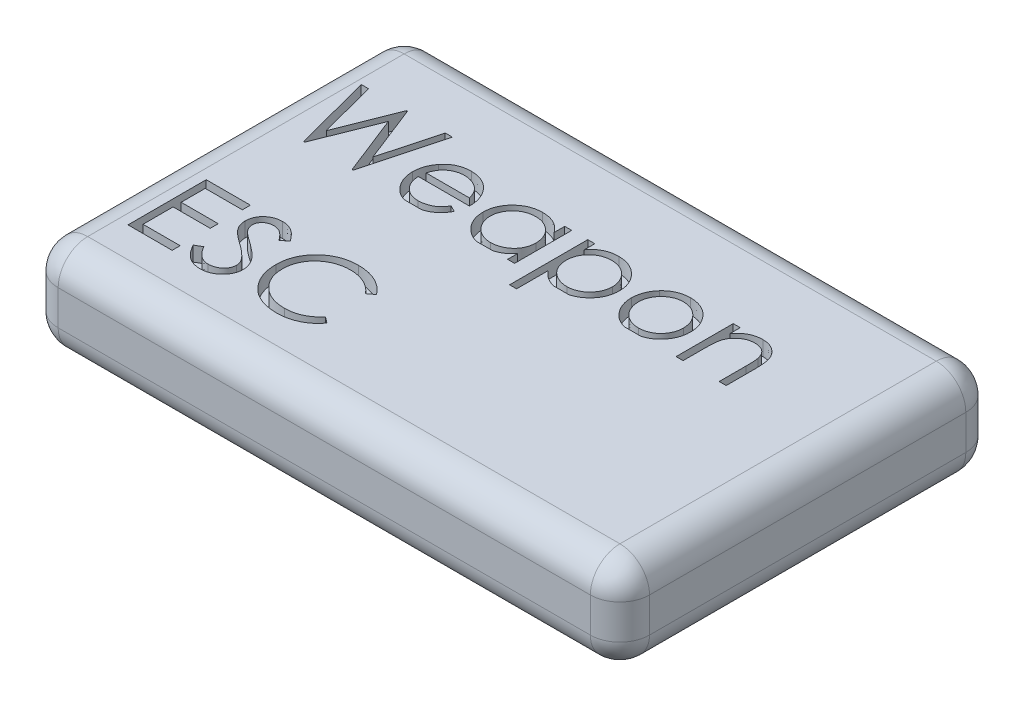
SolidWorks part; units mm, degrees
ref_plane "Front Plane" through (0, 0, 0) normal (0, 0, 1) x (1, 0, 0)
ref_plane "Top Plane" through (0, 0, 0) normal (0, 1, 0) x (1, 0, 0)
ref_plane "Right Plane" through (0, 0, 0) normal (1, 0, 0) x (0, 0, -1)
sketch "Sketch1" plane through (0, 0, 0) normal (0, 1, 0) x (1, 0, 0)
  line L1 (0, 0) -> (20, 0)
  line L2 (0, 0) -> (0, 12.7)
  line L3 (0, 12.7) -> (20, 12.7)
  line L4 (20, 0) -> (20, 12.7)
  dimension "D1" = 20
  dimension "D2" = 12.7
extrude "Boss-Extrude1" add sketch "Sketch1" along normal blind 3.175
fillet "Fillet1" radius 1 12 edges at (0, 0, -6.35) (10, 0, 0) (20, 0, -6.35) (10, 0, -12.7) (20, 3.175, -6.35) (10, 3.175, -12.7) (0, 1.5875, -12.7) (20, 1.5875, -12.7) (20, 1.5875, 0) (0, 1.5875, 0) (0, 3.175, -6.35) (10, 3.175, 0)
sketch "Sketch2" plane through (0, 3.175, 0) normal (0, 1, 0) x (1, 0, 0)
  line L0 (1, 7.4323) -> (19, 7.4323)
  line L1 (1, 11.7) -> (1, 1) construction
  line L2 (19, 1) -> (19, 11.7) construction
  line L3 (1.1696, 10.0782) -> (1.415, 10.0782)
  line L4 (1.415, 10.0782) -> (1.9328, 8.1378)
  line L5 (1.9328, 8.1378) -> (2.7029, 10.0782)
  line L6 (2.7029, 10.0782) -> (2.7374, 10.0782)
  line L7 (2.7374, 10.0782) -> (3.4932, 8.151)
  line L8 (3.4932, 8.151) -> (4.0137, 10.0782)
  line L9 (4.0137, 10.0782) -> (4.2564, 10.0782)
  line L10 (4.2564, 10.0782) -> (3.543, 7.4323)
  line L11 (3.543, 7.4323) -> (3.5091, 7.4323)
  line L12 (3.5091, 7.4323) -> (2.713, 9.4559)
  line L13 (2.713, 9.4559) -> (1.9074, 7.4323)
  line L14 (1.9074, 7.4323) -> (1.8735, 7.4323)
  line L15 (1.8735, 7.4323) -> (1.1696, 10.0782)
  line L16 (6.2503, 8.0429) -> (6.4613, 7.9321)
  line L17 (6.563, 8.3482) -> (4.8331, 8.3482)
  line L18 (4.858, 8.5856) -> (6.3256, 8.5856)
  line L19 (9.0053, 9.3658) -> (9.0053, 7.4323)
  line L20 (9.0053, 7.4323) -> (8.7679, 7.4323)
  line L21 (8.7679, 7.4323) -> (8.7679, 7.7668)
  line L22 (8.7679, 9.0081) -> (8.7679, 9.3658)
  line L23 (8.7679, 9.3658) -> (9.0053, 9.3658)
  line L24 (9.5481, 9.3658) -> (9.7855, 9.3658)
  line L25 (9.7855, 9.3658) -> (9.7855, 9.0081)
  line L26 (9.7855, 7.7827) -> (9.7855, 6.72)
  line L27 (9.7855, 6.72) -> (9.5481, 6.72)
  line L28 (9.5481, 6.72) -> (9.5481, 9.3658)
  line L29 (14.4666, 9.3658) -> (14.7041, 9.3658)
  line L30 (14.7041, 9.3658) -> (14.7041, 9.0171)
  line L31 (16.1627, 8.4197) -> (16.1627, 7.4323)
  line L32 (16.1627, 7.4323) -> (15.9252, 7.4323)
  line L33 (15.9252, 7.4323) -> (15.9252, 8.3418)
  line L34 (14.7041, 8.1314) -> (14.7041, 7.4323)
  line L35 (14.7041, 7.4323) -> (14.4666, 7.4323)
  line L36 (14.4666, 7.4323) -> (14.4666, 9.3658)
  line L37 (1.3392, 4.6684) -> (2.8317, 4.6684)
  line L38 (2.8317, 4.6684) -> (2.8317, 4.3971)
  line L39 (2.8317, 4.3971) -> (1.5767, 4.3971)
  line L40 (1.5767, 4.3971) -> (1.5767, 3.583)
  line L41 (1.5767, 3.583) -> (2.8317, 3.583)
  line L42 (2.8317, 3.583) -> (2.8317, 3.3116)
  line L43 (2.8317, 3.3116) -> (1.5767, 3.3116)
  line L44 (1.5767, 3.3116) -> (1.5767, 2.294)
  line L45 (1.5767, 2.294) -> (2.8317, 2.294)
  line L46 (2.8317, 2.294) -> (2.8317, 2.0226)
  line L47 (2.8317, 2.0226) -> (1.3392, 2.0226)
  line L48 (1.3392, 2.0226) -> (1.3392, 4.6684)
  line L49 (3.0353, 2.533) -> (3.2589, 2.6671)
  line L50 (4.5617, 4.2884) -> (4.347, 4.1257)
  line L51 (7.5807, 4.1829) -> (7.3729, 4.0239)
  line L52 (7.3729, 2.6671) -> (7.5807, 2.5097)
  spline S0 degree 3 poles (6.4613, 7.9321) (6.4299, 7.8734) (6.3774, 7.791) (6.2965, 7.6929) (6.2322, 7.6311) (6.1644, 7.5772) (6.0928, 7.5301) (6.017, 7.49) (5.937, 7.4561) (5.8521, 7.4301) (5.7293, 7.405) (5.6334, 7.3984) (5.5682, 7.3984) knots 0 0 0 0 0.181661 0.265874 0.346355 0.4246 0.501903 0.579992 0.658443 0.738672 0.821894 1 1 1 1
  spline S1 degree 3 poles (5.5682, 7.3984) (5.4958, 7.3984) (5.3893, 7.4067) (5.2538, 7.4394) (5.1606, 7.4726) (5.0739, 7.516) (4.9934, 7.5689) (4.9187, 7.631) (4.8521, 7.7028) (4.7922, 7.7797) (4.7394, 7.8597) (4.6952, 7.9429) (4.6592, 8.0285) (4.6302, 8.1161) (4.6029, 8.2374) (4.5963, 8.331) (4.5956, 8.3938) knots 0 0 0 0 0.139629 0.204797 0.268135 0.329814 0.391301 0.453434 0.516552 0.579631 0.641119 0.701294 0.76081 0.819932 0.87892 1 1 1 1
  spline S2 degree 3 poles (4.5956, 8.3938) (4.5963, 8.4526) (4.6018, 8.5404) (4.6257, 8.6542) (4.6501, 8.7365) (4.6815, 8.8163) (4.733, 8.9202) (4.7823, 8.9928) (4.8182, 9.0393) knots 0 0 0 0 0.253768 0.377428 0.500551 0.623296 0.746578 1 1 1 1
  spline S3 degree 3 poles (4.8182, 9.0393) (4.864, 9.0966) (4.9387, 9.1766) (5.0556, 9.2603) (5.1475, 9.3118) (5.246, 9.3508) (5.3871, 9.3905) (5.4988, 9.3988) (5.574, 9.3997) knots 0 0 0 0 0.253589 0.374643 0.49534 0.616325 0.739759 1 1 1 1
  spline S4 degree 3 poles (5.574, 9.3997) (5.6518, 9.4001) (5.7666, 9.3888) (5.9122, 9.3485) (6.0134, 9.3069) (6.1084, 9.2531) (6.228, 9.163) (6.3062, 9.0802) (6.3526, 9.0192) knots 0 0 0 0 0.259033 0.38188 0.502258 0.622752 0.744743 1 1 1 1
  spline S5 degree 3 poles (6.3526, 9.0192) (6.3873, 8.9747) (6.4326, 8.9024) (6.4807, 8.799) (6.5097, 8.7167) (6.5331, 8.6306) (6.5563, 8.5079) (6.5618, 8.4126) (6.563, 8.3482) knots 0 0 0 0 0.236255 0.356174 0.47725 0.60154 0.729618 1 1 1 1
  spline S6 degree 3 poles (4.8331, 8.3482) (4.8344, 8.2981) (4.8411, 8.2241) (4.864, 8.1295) (4.8876, 8.0636) (4.9163, 8.001) (4.9513, 7.9419) (4.9932, 7.8867) (5.0398, 7.8348) (5.0918, 7.7887) (5.1464, 7.7473) (5.2045, 7.7127) (5.2657, 7.6846) (5.3298, 7.6626) (5.4205, 7.6422) (5.4909, 7.6356) (5.5385, 7.6358) knots 0 0 0 0 0.134476 0.198391 0.260753 0.321829 0.383037 0.444653 0.507398 0.569825 0.630778 0.690929 0.750945 0.811049 0.872331 1 1 1 1
  spline S7 degree 3 poles (5.5385, 7.6358) (5.5855, 7.6356) (5.6561, 7.6412) (5.7482, 7.6604) (5.8156, 7.68) (5.8803, 7.7039) (5.9402, 7.7327) (5.9953, 7.7645) (6.0468, 7.801) (6.0968, 7.8456) (6.1674, 7.9248) (6.2182, 7.9926) (6.2503, 8.0429) knots 0 0 0 0 0.163879 0.245659 0.327726 0.40861 0.485749 0.559169 0.630268 0.705306 0.792065 1 1 1 1
  spline S8 degree 3 poles (6.3256, 8.5856) (6.3106, 8.6467) (6.2806, 8.7328) (6.2258, 8.8363) (6.1793, 8.901) (6.1265, 8.9584) (6.0655, 9.0087) (5.9972, 9.0536) (5.9217, 9.0915) (5.8419, 9.1237) (5.7302, 9.1529) (5.644, 9.1632) (5.5862, 9.1623) knots 0 0 0 0 0.185231 0.267501 0.3444 0.419595 0.496891 0.576638 0.660268 0.745387 0.83004 1 1 1 1
  spline S9 degree 3 poles (5.5862, 9.1623) (5.5394, 9.1624) (5.4698, 9.1573) (5.3804, 9.1379) (5.3163, 9.1183) (5.2554, 9.0921) (5.176, 9.051) (5.1224, 9.01) (5.088, 8.981) knots 0 0 0 0 0.259141 0.384162 0.505992 0.629098 0.750669 1 1 1 1
  spline S10 degree 3 poles (5.088, 8.981) (5.0616, 8.9588) (5.0259, 8.9203) (4.9831, 8.8638) (4.9533, 8.8162) (4.926, 8.7643) (4.8911, 8.6882) (4.8704, 8.6275) (4.858, 8.5856) knots 0 0 0 0 0.22258 0.3385 0.458709 0.585535 0.717518 1 1 1 1
  spline S11 degree 3 poles (8.7679, 7.7668) (8.7171, 7.7067) (8.635, 7.6231) (8.5091, 7.5365) (8.4118, 7.4849) (8.3098, 7.4463) (8.1661, 7.4089) (8.0539, 7.3978) (7.9782, 7.3984) knots 0 0 0 0 0.262085 0.38627 0.507165 0.6273 0.748145 1 1 1 1
  spline S12 degree 3 poles (7.9782, 7.3984) (7.9109, 7.3986) (7.8109, 7.4073) (7.6823, 7.4381) (7.5906, 7.4698) (7.5032, 7.5118) (7.4192, 7.5621) (7.3392, 7.622) (7.2643, 7.6905) (7.1954, 7.7649) (7.1348, 7.8442) (7.0844, 7.9282) (7.0422, 8.0156) (7.0097, 8.1073) (6.9789, 8.2364) (6.9702, 8.3367) (6.9701, 8.4044) knots 0 0 0 0 0.127433 0.189004 0.24993 0.310668 0.372329 0.434939 0.499576 0.564191 0.626735 0.688109 0.749294 0.810331 0.871901 1 1 1 1
  spline S13 degree 3 poles (6.9701, 8.4044) (6.9705, 8.4708) (6.9786, 8.5695) (7.0103, 8.6963) (7.0432, 8.7865) (7.0854, 8.873) (7.1368, 8.9557) (7.1973, 9.0349) (7.267, 9.1087) (7.3426, 9.1769) (7.4234, 9.2362) (7.5075, 9.2874) (7.5961, 9.3279) (7.688, 9.3607) (7.8174, 9.3915) (7.918, 9.3991) (7.9856, 9.3997) knots 0 0 0 0 0.126079 0.186904 0.247574 0.308003 0.369132 0.432033 0.496791 0.561611 0.624914 0.686726 0.748079 0.809582 0.871631 1 1 1 1
  spline S14 degree 3 poles (7.9856, 9.3997) (8.0628, 9.3995) (8.1776, 9.3896) (8.3227, 9.3488) (8.4245, 9.3081) (8.5206, 9.2539) (8.643, 9.1608) (8.7211, 9.0723) (8.7679, 9.0081) knots 0 0 0 0 0.254654 0.376015 0.495255 0.614798 0.738106 1 1 1 1
  spline S15 degree 3 poles (7.9888, 9.1623) (7.9204, 9.162) (7.818, 9.1506) (7.6887, 9.1079) (7.5973, 9.0646) (7.5121, 9.0102) (7.436, 8.9443) (7.3683, 8.8688) (7.3114, 8.7841) (7.265, 8.6932) (7.2213, 8.5669) (7.2067, 8.4678) (7.2075, 8.4017) knots 0 0 0 0 0.169593 0.252476 0.336244 0.419505 0.502036 0.584775 0.669846 0.754185 0.836658 1 1 1 1
  spline S16 degree 3 poles (7.2075, 8.4017) (7.2081, 8.336) (7.2207, 8.2366) (7.2659, 8.1105) (7.3122, 8.0188) (7.3702, 7.9337) (7.4374, 7.8568) (7.5144, 7.7907) (7.5998, 7.7353) (7.691, 7.6906) (7.8191, 7.6488) (7.9194, 7.6355) (7.9867, 7.6358) knots 0 0 0 0 0.162859 0.245484 0.330807 0.416493 0.499893 0.583048 0.667158 0.751312 0.833785 1 1 1 1
  spline S17 degree 3 poles (7.9867, 7.6358) (8.0549, 7.6361) (8.1575, 7.648) (8.2881, 7.6903) (8.3817, 7.734) (8.4689, 7.7883) (8.5471, 7.8518) (8.6132, 7.9257) (8.6693, 8.0068) (8.7133, 8.0958) (8.7568, 8.2239) (8.7675, 8.3263) (8.7679, 8.3948) knots 0 0 0 0 0.168664 0.252552 0.33824 0.423103 0.505556 0.586176 0.667136 0.748499 0.830452 1 1 1 1
  spline S18 degree 3 poles (8.7679, 8.3948) (8.7677, 8.4474) (8.7611, 8.5253) (8.7375, 8.6252) (8.713, 8.6958) (8.6809, 8.7629) (8.6422, 8.8267) (8.5961, 8.8871) (8.5435, 8.9431) (8.4859, 8.9942) (8.425, 9.0399) (8.36, 9.0774) (8.2921, 9.1084) (8.221, 9.133) (8.12, 9.1555) (8.0418, 9.1631) (7.9888, 9.1623) knots 0 0 0 0 0.129188 0.191219 0.251913 0.312507 0.373494 0.435152 0.498741 0.562095 0.624187 0.685476 0.746097 0.807612 0.869967 1 1 1 1
  spline S19 degree 3 poles (9.7855, 9.0081) (9.8325, 9.0725) (9.9115, 9.1602) (10.0334, 9.2541) (10.1295, 9.308) (10.2311, 9.3487) (10.3757, 9.3896) (10.4899, 9.3995) (10.5668, 9.3997) knots 0 0 0 0 0.263045 0.386061 0.505771 0.625178 0.746148 1 1 1 1
  spline S20 degree 3 poles (10.5668, 9.3997) (10.6345, 9.3991) (10.7353, 9.3915) (10.8649, 9.3607) (10.9568, 9.3279) (11.0454, 9.2874) (11.1295, 9.2362) (11.2103, 9.1769) (11.2859, 9.1087) (11.3556, 9.0349) (11.416, 8.9555) (11.4681, 8.8731) (11.5102, 8.7865) (11.5431, 8.6963) (11.5748, 8.5695) (11.5829, 8.4708) (11.5833, 8.4044) knots 0 0 0 0 0.128636 0.190653 0.252125 0.313446 0.375227 0.438498 0.503285 0.56801 0.630879 0.692154 0.752552 0.813191 0.873985 1 1 1 1
  spline S21 degree 3 poles (11.5833, 8.4044) (11.5832, 8.3367) (11.5745, 8.2364) (11.5437, 8.1073) (11.5112, 8.0157) (11.4691, 7.928) (11.418, 7.8444) (11.3576, 7.7648) (11.2886, 7.6905) (11.2137, 7.622) (11.1336, 7.5621) (11.0497, 7.5118) (10.9622, 7.4698) (10.8706, 7.4381) (10.7418, 7.4072) (10.6417, 7.3986) (10.5742, 7.3984) knots 0 0 0 0 0.128034 0.189574 0.25058 0.311733 0.37325 0.435763 0.500346 0.564949 0.627528 0.689157 0.749865 0.81076 0.8723 1 1 1 1
  spline S22 degree 3 poles (10.5742, 7.3984) (10.4982, 7.3975) (10.386, 7.4105) (10.2421, 7.4502) (10.1406, 7.493) (10.0438, 7.5477) (9.919, 7.638) (9.8366, 7.7221) (9.7855, 7.7827) knots 0 0 0 0 0.250548 0.37123 0.492116 0.613401 0.737997 1 1 1 1
  spline S23 degree 3 poles (10.5646, 9.1623) (10.5116, 9.1631) (10.4335, 9.1555) (10.3324, 9.1331) (10.2613, 9.1082) (10.193, 9.0777) (10.1283, 9.0395) (10.067, 8.9944) (10.0094, 8.9433) (9.9573, 8.8869) (9.9112, 8.8267) (9.8725, 8.7628) (9.8404, 8.6958) (9.816, 8.6252) (9.7924, 8.5253) (9.7857, 8.4474) (9.7855, 8.3948) knots 0 0 0 0 0.130024 0.192374 0.253884 0.314896 0.375806 0.438242 0.501591 0.564881 0.626533 0.687516 0.748106 0.808796 0.870822 1 1 1 1
  spline S24 degree 3 poles (9.7855, 8.3948) (9.7856, 8.3262) (9.7971, 8.2241) (9.8394, 8.0957) (9.8836, 8.0069) (9.9396, 7.9253) (10.0069, 7.8522) (10.0851, 7.7881) (10.1728, 7.7341) (10.2669, 7.6903) (10.3978, 7.6482) (10.5002, 7.636) (10.5684, 7.6358) knots 0 0 0 0 0.169344 0.251061 0.332326 0.413189 0.494299 0.576654 0.661785 0.747765 0.831967 1 1 1 1
  spline S25 degree 3 poles (10.5684, 7.6358) (10.6352, 7.6354) (10.7352, 7.649) (10.8629, 7.6905) (10.9537, 7.7355) (11.039, 7.7907) (11.116, 7.8568) (11.1833, 7.9336) (11.2407, 8.019) (11.2868, 8.1106) (11.3331, 8.2364) (11.3451, 8.3361) (11.3459, 8.4017) knots 0 0 0 0 0.165574 0.248159 0.332033 0.416257 0.499525 0.583039 0.668596 0.754035 0.83692 1 1 1 1
  spline S26 degree 3 poles (11.3459, 8.4017) (11.3468, 8.4679) (11.332, 8.5668) (11.2885, 8.6934) (11.2413, 8.7838) (11.1852, 8.869) (11.1174, 8.9443) (11.0413, 9.0102) (10.9561, 9.0646) (10.8647, 9.1079) (10.7354, 9.1506) (10.6331, 9.162) (10.5646, 9.1623) knots 0 0 0 0 0.163349 0.245826 0.330367 0.415198 0.497941 0.580476 0.66374 0.747513 0.830399 1 1 1 1
  spline S27 degree 3 poles (12.9921, 9.3997) (13.0632, 9.4005) (13.1685, 9.3902) (13.3031, 9.3565) (13.3982, 9.3223) (13.4877, 9.2764) (13.6029, 9.2026) (13.6797, 9.1326) (13.7267, 9.0812) knots 0 0 0 0 0.258332 0.382134 0.503804 0.624693 0.746871 1 1 1 1
  spline S28 degree 3 poles (13.7267, 9.0812) (13.7698, 9.0341) (13.8276, 8.9585) (13.8897, 8.8494) (13.9269, 8.7646) (13.9561, 8.6766) (13.9842, 8.5534) (13.9914, 8.458) (13.9917, 8.3938) knots 0 0 0 0 0.253834 0.376506 0.498534 0.621368 0.744565 1 1 1 1
  spline S29 degree 3 poles (13.9917, 8.3938) (13.9921, 8.3291) (13.9833, 8.233) (13.954, 8.1087) (13.9232, 8.0196) (13.8836, 7.9335) (13.8353, 7.8508) (13.778, 7.7713) (13.713, 7.6957) (13.6411, 7.6261) (13.5632, 7.5653) (13.4806, 7.5133) (13.3925, 7.4714) (13.2994, 7.4384) (13.1663, 7.4067) (13.0624, 7.3987) (12.9921, 7.3984) knots 0 0 0 0 0.123337 0.183265 0.243172 0.302898 0.363774 0.425605 0.489659 0.553785 0.616222 0.677854 0.739517 0.802097 0.865866 1 1 1 1
  spline S30 degree 3 poles (12.9921, 7.3984) (12.9215, 7.3987) (12.8172, 7.4067) (12.6837, 7.4384) (12.5906, 7.4715) (12.502, 7.5133) (12.419, 7.5652) (12.341, 7.6261) (12.2691, 7.6957) (12.2041, 7.7713) (12.1468, 7.8508) (12.0985, 7.9335) (12.0589, 8.0196) (12.0281, 8.1087) (11.9989, 8.233) (11.99, 8.3291) (11.9904, 8.3938) knots 0 0 0 0 0.134635 0.198324 0.260825 0.322714 0.384555 0.446913 0.510958 0.574931 0.636685 0.697483 0.757134 0.816966 0.876818 1 1 1 1
  spline S31 degree 3 poles (11.9904, 8.3938) (11.9908, 8.4578) (11.998, 8.553) (12.026, 8.6759) (12.0552, 8.7635) (12.0927, 8.848) (12.154, 8.9574) (12.2127, 9.0324) (12.2554, 9.0796) knots 0 0 0 0 0.255238 0.378679 0.501088 0.622714 0.746241 1 1 1 1
  spline S32 degree 3 poles (12.2554, 9.0796) (12.302, 9.1317) (12.3795, 9.2011) (12.4944, 9.2763) (12.5849, 9.3213) (12.6799, 9.3567) (12.8151, 9.3902) (12.9206, 9.4004) (12.9921, 9.3997) knots 0 0 0 0 0.252713 0.374819 0.496436 0.617911 0.741288 1 1 1 1
  spline S33 degree 3 poles (12.9911, 9.1623) (12.9404, 9.1622) (12.8652, 9.1553) (12.7684, 9.1318) (12.6993, 9.1072) (12.6331, 9.0754) (12.5696, 9.0363) (12.5088, 8.9904) (12.4518, 8.9379) (12.3995, 8.8806) (12.3538, 8.8194) (12.3149, 8.7556) (12.2826, 8.6888) (12.2585, 8.6186) (12.2347, 8.5202) (12.228, 8.4437) (12.2278, 8.3922) knots 0 0 0 0 0.126044 0.187165 0.247399 0.30838 0.36978 0.432584 0.497641 0.562401 0.625557 0.687332 0.748313 0.809791 0.871768 1 1 1 1
  spline S34 degree 3 poles (12.2278, 8.3922) (12.228, 8.3251) (12.2398, 8.2244) (12.2839, 8.0974) (12.3281, 8.007) (12.3836, 7.9233) (12.449, 7.8487) (12.5236, 7.7843) (12.6065, 7.7309) (12.6959, 7.6885) (12.8232, 7.6477) (12.9235, 7.6351) (12.9911, 7.6358) knots 0 0 0 0 0.168179 0.251488 0.335841 0.419834 0.502345 0.583649 0.665931 0.748717 0.831047 1 1 1 1
  spline S35 degree 3 poles (12.9911, 7.6358) (13.0585, 7.6352) (13.1588, 7.6475) (13.2858, 7.6886) (13.3752, 7.7308) (13.458, 7.7845) (13.5331, 7.8483) (13.5979, 7.9235) (13.6534, 8.0071) (13.6983, 8.0972) (13.7422, 8.2244) (13.7542, 8.3251) (13.7543, 8.3922) knots 0 0 0 0 0.168983 0.250908 0.333708 0.416005 0.49766 0.579893 0.663902 0.748466 0.831791 1 1 1 1
  spline S36 degree 3 poles (13.7543, 8.3922) (13.7541, 8.4437) (13.7474, 8.5202) (13.7237, 8.6186) (13.6995, 8.6888) (13.6673, 8.7557) (13.6276, 8.8193) (13.5821, 8.8808) (13.5292, 8.9377) (13.4723, 8.9904) (13.4114, 9.0363) (13.3481, 9.0752) (13.282, 9.1075) (13.2129, 9.1316) (13.1165, 9.1555) (13.0415, 9.162) (12.9911, 9.1623) knots 0 0 0 0 0.128274 0.19027 0.251768 0.312769 0.374793 0.43797 0.503047 0.568125 0.63095 0.692369 0.752973 0.813641 0.874355 1 1 1 1
  spline S37 degree 3 poles (14.7041, 9.0171) (14.752, 9.0792) (14.8282, 9.1661) (14.9472, 9.2572) (15.0378, 9.3102) (15.1328, 9.3501) (15.2655, 9.3891) (15.3698, 9.3994) (15.4397, 9.3997) knots 0 0 0 0 0.273569 0.398988 0.51993 0.63811 0.756589 1 1 1 1
  spline S38 degree 3 poles (15.4397, 9.3997) (15.5096, 9.3993) (15.6138, 9.3879) (15.7427, 9.3405) (15.8309, 9.2928) (15.9104, 9.2333) (15.9801, 9.1641) (16.0379, 9.0845) (16.0766, 9.0106) (16.1021, 8.9451) (16.1181, 8.8889) (16.1317, 8.8264) (16.1436, 8.7577) (16.1516, 8.6822) (16.1603, 8.569) (16.1632, 8.4807) (16.1627, 8.4197) knots 0 0 0 0 0.151178 0.223488 0.295543 0.366976 0.437131 0.507044 0.57856 0.616614 0.658756 0.704491 0.754803 0.809332 0.868274 1 1 1 1
  spline S39 degree 3 poles (15.9252, 8.3418) (15.9248, 8.3922) (15.9248, 8.4643) (15.9218, 8.556) (15.9188, 8.6145) (15.9144, 8.6661) (15.9089, 8.7212) (15.9025, 8.759) (15.8971, 8.7817) knots 0 0 0 0 0.34211 0.489826 0.623254 0.74008 0.841483 1 1 1 1
  spline S40 degree 3 poles (15.8971, 8.7817) (15.8839, 8.8398) (15.8539, 8.9227) (15.7872, 9.0146) (15.7283, 9.0692) (15.6593, 9.1116) (15.5502, 9.1526) (15.4601, 9.1626) (15.3984, 9.1623) knots 0 0 0 0 0.260833 0.378476 0.493178 0.609281 0.729981 1 1 1 1
  spline S41 degree 3 poles (15.3984, 9.1623) (15.3606, 9.1625) (15.3041, 9.1582) (15.2311, 9.1424) (15.1778, 9.1266) (15.1268, 9.1049) (15.0763, 9.0804) (15.0283, 9.0497) (14.9817, 9.0155) (14.9384, 8.9777) (14.8981, 8.9377) (14.8622, 8.8952) (14.8296, 8.8507) (14.8015, 8.8038) (14.7686, 8.7382) (14.7501, 8.686) (14.7406, 8.6503) knots 0 0 0 0 0.126627 0.188984 0.25023 0.312351 0.374574 0.438148 0.50292 0.567974 0.630771 0.692935 0.754398 0.815218 0.876117 1 1 1 1
  spline S42 degree 3 poles (14.7406, 8.6503) (14.7336, 8.622) (14.7257, 8.5756) (14.7178, 8.5083) (14.7125, 8.4472) (14.7092, 8.3786) (14.7043, 8.2726) (14.7044, 8.1893) (14.7041, 8.1314) knots 0 0 0 0 0.167615 0.271052 0.38946 0.520843 0.666399 1 1 1 1
  spline S43 degree 3 poles (3.2589, 2.6671) (3.2977, 2.5999) (3.3588, 2.5056) (3.455, 2.3988) (3.5268, 2.3361) (3.6011, 2.2869) (3.7031, 2.2404) (3.7854, 2.226) (3.8398, 2.2261) knots 0 0 0 0 0.304646 0.438547 0.562322 0.677433 0.786897 1 1 1 1
  spline S44 degree 3 poles (3.8398, 2.2261) (3.8858, 2.2257) (3.9544, 2.2338) (4.0425, 2.2593) (4.1049, 2.2863) (4.1632, 2.3191) (4.2143, 2.3587) (4.2585, 2.403) (4.2946, 2.4524) (4.3223, 2.5056) (4.3508, 2.5782) (4.3575, 2.6364) (4.3582, 2.6745) knots 0 0 0 0 0.18093 0.270088 0.360156 0.448343 0.532666 0.613834 0.693982 0.772716 0.849335 1 1 1 1
  spline S45 degree 3 poles (4.3582, 2.6745) (4.3584, 2.7193) (4.3404, 2.8129) (4.2921, 2.8948) (4.2633, 2.9342) knots 0 0 0 0 0.477158 1 1 1 1
  spline S46 degree 3 poles (4.2633, 2.9342) (4.2389, 2.9664) (4.1977, 3.0152) (4.1336, 3.0774) (4.0778, 3.1296) (4.0142, 3.1827) (3.9183, 3.261) (3.8402, 3.3173) (3.7863, 3.3561) knots 0 0 0 0 0.18953 0.299198 0.418926 0.548376 0.688136 1 1 1 1
  spline S47 degree 3 poles (3.7863, 3.3561) (3.7327, 3.3936) (3.6578, 3.4492) (3.5642, 3.5216) (3.5058, 3.5686) (3.4557, 3.6114) (3.4035, 3.6581) (3.371, 3.6934) (3.3527, 3.716) knots 0 0 0 0 0.347082 0.495568 0.628357 0.74552 0.845831 1 1 1 1
  spline S48 degree 3 poles (3.3527, 3.716) (3.3293, 3.7463) (3.2967, 3.7928) (3.2619, 3.8591) (3.2416, 3.9093) (3.2246, 3.9602) (3.2092, 4.0297) (3.2047, 4.0831) (3.2049, 4.1188) knots 0 0 0 0 0.262559 0.388264 0.512667 0.633722 0.755394 1 1 1 1
  spline S49 degree 3 poles (3.2049, 4.1188) (3.2047, 4.1742) (3.2152, 4.2565) (3.2504, 4.3603) (3.2869, 4.4332) (3.3339, 4.4997) (3.3884, 4.5606) (3.4533, 4.6118) (3.5245, 4.6566) (3.6024, 4.6916) (3.712, 4.7273) (3.799, 4.7355) (3.8568, 4.7363) knots 0 0 0 0 0.16578 0.24628 0.327461 0.408797 0.489715 0.571376 0.655523 0.741019 0.826547 1 1 1 1
  spline S50 degree 3 poles (3.8568, 4.7363) (3.9187, 4.7364) (4.0117, 4.725) (4.129, 4.6837) (4.1996, 4.6488) (4.2549, 4.6139) (4.2971, 4.5821) (4.3398, 4.5456) (4.3834, 4.5041) (4.4272, 4.4573) (4.4885, 4.3863) (4.5329, 4.329) (4.5617, 4.2884) knots 0 0 0 0 0.213252 0.31883 0.426794 0.483646 0.543604 0.608308 0.677127 0.750686 0.828713 1 1 1 1
  spline S51 degree 3 poles (4.347, 4.1257) (4.3224, 4.1581) (4.2851, 4.2036) (4.2355, 4.2607) (4.2003, 4.2965) (4.1675, 4.3287) (4.1357, 4.3564) (4.1053, 4.3796) (4.0669, 4.4045) (4.0188, 4.4291) (3.9376, 4.4571) (3.8733, 4.4646) (3.8303, 4.4649) knots 0 0 0 0 0.189629 0.274184 0.352183 0.423199 0.488551 0.548473 0.60144 0.701198 0.799592 1 1 1 1
  spline S52 degree 3 poles (3.8303, 4.4649) (3.7777, 4.4657) (3.7004, 4.4544) (3.6081, 4.4125) (3.5502, 4.37) (3.502, 4.3195) (3.4551, 4.2419) (3.4424, 4.1745) (3.4423, 4.1299) knots 0 0 0 0 0.275903 0.402371 0.528414 0.650356 0.765895 1 1 1 1
  spline S53 degree 3 poles (3.4423, 4.1299) (3.4414, 4.1015) (3.4479, 4.0592) (3.4622, 4.0037) (3.479, 3.9621) (3.5024, 3.9202) (3.5456, 3.8592) (3.5869, 3.8168) (3.6167, 3.7881) knots 0 0 0 0 0.214746 0.322939 0.434116 0.553412 0.686073 1 1 1 1
  spline S54 degree 3 poles (3.6167, 3.7881) (3.6303, 3.7756) (3.6551, 3.7551) (3.6946, 3.7257) (3.735, 3.695) (3.7834, 3.6595) (3.8635, 3.6024) (3.927, 3.5565) (3.9723, 3.5247) knots 0 0 0 0 0.124952 0.218094 0.333502 0.468789 0.624938 1 1 1 1
  spline S55 degree 3 poles (3.9723, 3.5247) (4.028, 3.4843) (4.1084, 3.4252) (4.2075, 3.3431) (4.2721, 3.2853) (4.3302, 3.2297) (4.3812, 3.1756) (4.4256, 3.1234) (4.4733, 3.0565) (4.5221, 2.9742) (4.5773, 2.8425) (4.5956, 2.7389) (4.5956, 2.6708) knots 0 0 0 0 0.187773 0.272396 0.351321 0.424335 0.491909 0.554233 0.611268 0.716348 0.81454 1 1 1 1
  spline S56 degree 3 poles (4.5956, 2.6708) (4.5964, 2.6238) (4.5887, 2.5542) (4.5662, 2.4641) (4.5413, 2.3999) (4.5108, 2.3374) (4.4721, 2.2781) (4.4273, 2.2208) (4.3759, 2.167) (4.3196, 2.1176) (4.2601, 2.0736) (4.1973, 2.037) (4.1316, 2.0071) (4.0629, 1.9837) (3.966, 1.9607) (3.8906, 1.9546) (3.8398, 1.9548) knots 0 0 0 0 0.121775 0.18092 0.240256 0.300114 0.361146 0.423501 0.488669 0.553954 0.617581 0.680238 0.742187 0.804663 0.868259 1 1 1 1
  spline S57 degree 3 poles (3.8398, 1.9548) (3.8001, 1.9545) (3.7411, 1.9593) (3.6638, 1.9723) (3.6082, 1.9876) (3.5537, 2.0061) (3.5007, 2.0288) (3.4491, 2.0561) (3.3985, 2.0874) (3.3493, 2.1237) (3.3017, 2.166) (3.2543, 2.2131) (3.2084, 2.2664) (3.1632, 2.3248) (3.1031, 2.4129) (3.0618, 2.4837) (3.0353, 2.533) knots 0 0 0 0 0.113696 0.169178 0.224159 0.27872 0.333794 0.389241 0.445822 0.503704 0.564294 0.627975 0.695038 0.765373 0.839611 1 1 1 1
  spline S58 degree 3 poles (7.3729, 4.0239) (7.344, 4.0594) (7.2982, 4.1102) (7.2319, 4.1721) (7.1806, 4.2154) (7.1263, 4.2543) (7.0705, 4.2908) (7.0121, 4.3235) (6.9314, 4.3631) (6.8259, 4.4045) (6.6463, 4.4516) (6.5061, 4.4654) (6.4114, 4.4649) knots 0 0 0 0 0.125475 0.187121 0.248294 0.309295 0.36985 0.430973 0.492456 0.616148 0.740844 1 1 1 1
  spline S59 degree 3 poles (6.4114, 4.4649) (6.3586, 4.4656) (6.28, 4.4599) (6.1769, 4.4447) (6.1015, 4.428) (6.0277, 4.4068) (5.9551, 4.3816) (5.8846, 4.3503) (5.8154, 4.3157) (5.749, 4.2767) (5.6862, 4.2341) (5.6273, 4.1885) (5.572, 4.1396) (5.5205, 4.0877) (5.473, 4.0323) (5.4298, 3.9734) (5.3899, 3.912) (5.3543, 3.8481) (5.3244, 3.7815) (5.2979, 3.7134) (5.277, 3.6429) (5.2604, 3.5707) (5.2449, 3.4708) (5.2395, 3.3945) (5.2401, 3.3429) knots 0 0 0 0 0.087502 0.130463 0.172752 0.215403 0.25765 0.300153 0.343121 0.385925 0.427686 0.468818 0.509492 0.549883 0.58998 0.630405 0.670869 0.711384 0.751627 0.791776 0.832459 0.873319 0.914543 1 1 1 1
  spline S60 degree 3 poles (5.2401, 3.3429) (5.2398, 3.2661) (5.2505, 3.1526) (5.285, 3.0068) (5.3229, 2.9044) (5.3697, 2.8062) (5.4289, 2.7138) (5.4974, 2.6258) (5.5762, 2.5443) (5.6627, 2.4698) (5.7555, 2.4042) (5.8543, 2.3496) (5.9582, 2.3041) (6.0678, 2.2692) (6.224, 2.2356) (6.3455, 2.2255) (6.4279, 2.2261) knots 0 0 0 0 0.12629 0.186726 0.246146 0.305576 0.365429 0.426326 0.48884 0.551725 0.613919 0.675484 0.737334 0.800229 0.864502 1 1 1 1
  spline S61 degree 3 poles (6.4279, 2.2261) (6.5187, 2.2261) (6.6537, 2.2389) (6.8259, 2.2858) (6.9479, 2.334) (7.0638, 2.3968) (7.2131, 2.4999) (7.3119, 2.5969) (7.3729, 2.6671) knots 0 0 0 0 0.252949 0.374755 0.49594 0.617181 0.740909 1 1 1 1
  spline S62 degree 3 poles (7.5807, 2.5097) (7.5479, 2.4662) (7.4959, 2.4037) (7.4196, 2.3273) (7.3594, 2.2743) (7.2966, 2.2243) (7.23, 2.1787) (7.1606, 2.1369) (7.0885, 2.0986) (7.0139, 2.0647) (6.9367, 2.0356) (6.8575, 2.0106) (6.7761, 1.99) (6.6924, 1.9739) (6.5769, 1.9593) (6.4888, 1.9543) (6.4295, 1.9548) knots 0 0 0 0 0.123053 0.183475 0.243727 0.304279 0.364863 0.425946 0.487391 0.54922 0.611144 0.673529 0.736961 0.800785 0.866013 1 1 1 1
  spline S63 degree 3 poles (6.4295, 1.9548) (6.3732, 1.9541) (6.29, 1.9586) (6.1808, 1.9704) (6.1023, 1.9834) (6.0259, 1.9988) (5.9521, 2.0194) (5.8804, 2.0425) (5.8108, 2.0696) (5.7435, 2.1002) (5.6786, 2.1349) (5.6161, 2.1732) (5.5555, 2.2143) (5.4976, 2.2597) (5.4229, 2.3252) (5.3707, 2.3792) (5.3382, 2.4175) knots 0 0 0 0 0.13775 0.203917 0.26878 0.332414 0.394754 0.45618 0.516996 0.577396 0.637198 0.696999 0.756756 0.816554 0.876948 1 1 1 1
  spline S64 degree 3 poles (5.3382, 2.4175) (5.2833, 2.4815) (5.2096, 2.5842) (5.1317, 2.7326) (5.0845, 2.8486) (5.0477, 2.9695) (5.0129, 3.14) (5.0024, 3.2718) (5.0027, 3.3609) knots 0 0 0 0 0.247156 0.36878 0.490734 0.613614 0.738958 1 1 1 1
  spline S65 degree 3 poles (5.0027, 3.3609) (5.0026, 3.4545) (5.0145, 3.5932) (5.0575, 3.7712) (5.1023, 3.8968) (5.1593, 4.0171) (5.2296, 4.1311) (5.3125, 4.2396) (5.4073, 4.3409) (5.5113, 4.4336) (5.6227, 4.5151) (5.7412, 4.5829) (5.8656, 4.6396) (5.9967, 4.6831) (6.1831, 4.7247) (6.3282, 4.7361) (6.4263, 4.7363) knots 0 0 0 0 0.127014 0.187955 0.248014 0.307748 0.368235 0.42947 0.492743 0.556258 0.618217 0.679655 0.741246 0.803415 0.866815 1 1 1 1
  spline S66 degree 3 poles (6.4263, 4.7363) (6.4864, 4.7364) (6.5757, 4.7323) (6.6925, 4.7164) (6.7769, 4.7005) (6.8594, 4.6807) (6.9394, 4.6548) (7.0173, 4.6253) (7.0927, 4.5913) (7.1652, 4.5532) (7.2348, 4.5113) (7.3009, 4.4657) (7.3641, 4.4168) (7.4231, 4.3636) (7.4989, 4.2887) (7.5488, 4.2258) (7.5807, 4.1829) knots 0 0 0 0 0.135683 0.201215 0.265682 0.329267 0.392395 0.45507 0.517127 0.57879 0.63974 0.700192 0.759806 0.819628 0.879355 1 1 1 1
  point P6 (0, 0)
extrude "Cut-Extrude1" cut sketch "Sketch2" against normal blind 0.5 contours L15 L0 L13 L12 L10 L9 L8 L7 L6 L5 L4 L3 | S7 S6 L17 S5 S4 S3 S2 S1 L0 S0 L16 S10 S9 S8 L18 | S14 S13 S12 L0 S11 L21 L19 L23 L22 S18 S17 S16 S15 | S22 L0 S21 S20 S19 L25 L24 L28 L26 S26 S25 S24 S23 | L28 L27 L26 L0 | S32 S31 S30 L0 S29 S28 S27 S36 S35 S34 S33 | S42 S41 S40 S39 L33 L0 L31 S38 S37 L30 L29 L36 L34 | L48 L47 L46 L45 L44 L43 L42 L41 L40 L39 L38 L37 | S57 S56 S55 S54 S53 S52 S51 L50 S50 S49 S48 S47 S46 S45 S44 S43 L49 | S66 S65 S64 S63 S62 L52 S61 S60 S59 S58 L51 region at (1.5608, 3.175, -8.7657) region at (14.4926, 3.175, -8.3991) region at (12.2127, 3.175, -7.8085) region at (9.5764, 3.175, -8.3991) region at (9.6668, 3.175, -7.0762) region at (7.1966, 3.175, -7.8108) region at (5.528, 3.175, -8.4289) region at (1.9201, 3.175, -3.3665) region at (3.8684, 3.175, -3.3111) region at (7.4537, 3.175, -4.1336)
